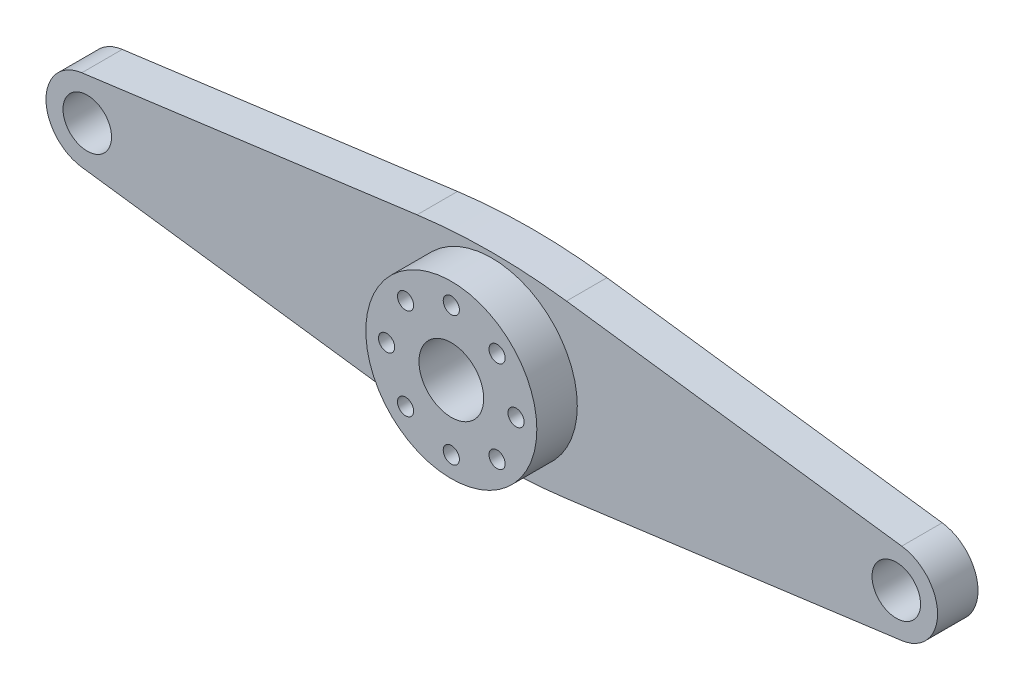
SolidWorks part; units mm, degrees
material "ABS"
ref_plane "Płaszczyzna przednia" through (0, 0, 0) normal (0, 0, 1) x (1, 0, 0)
ref_plane "Płaszczyzna górna" through (0, 0, 0) normal (0, 1, 0) x (1, 0, 0)
ref_plane "Płaszczyzna prawa" through (0, 0, 0) normal (1, 0, 0) x (0, 0, -1)
sketch "Szkic1" plane through (0, 0, 0) normal (0, 0, 1) x (1, 0, 0)
  line L0 (-44.521, 0) -> (57.4684, 0) construction
  line L1 (0, 0) -> (0, 26.3225) construction
  line L2 (-50.6729, 5.0557) -> (-9.2351, 10.5708)
  line L3 (-50.6729, -5.0557) -> (-9.2351, -10.5708)
  line L4 (50.6729, -5.0557) -> (9.2351, -10.5708)
  line L5 (50.6729, 5.0557) -> (9.2351, 10.5708)
  circle A0 centre (0, 0) radius 4
  circle A1 centre (-5.6569, 5.6569) radius 1
  circle A2 centre (-8, 0) radius 1
  circle A3 centre (0, 8) radius 1
  circle A4 centre (5.6569, 5.6569) radius 1
  circle A5 centre (-50, 0) radius 3
  circle A6 centre (50, 0) radius 3
  arc A7 (-50.6729, 5.0557) -> (-50.6729, -5.0557) centre (-50, 0) ccw
  arc A8 (50.6729, 5.0557) -> (50.6729, -5.0557) centre (50, 0) cw
  arc A9 (-9.2351, 10.5708) -> (9.2351, 10.5708) centre (0, -58.8174) cw
  arc A10 (-9.2351, -10.5708) -> (9.2351, -10.5708) centre (0, 58.8174) ccw
  circle A11 centre (8, 0) radius 1
  circle A12 centre (5.6569, -5.6569) radius 1
  circle A13 centre (0, -8) radius 1
  circle A14 centre (-5.6569, -5.6569) radius 1
  circle A15 centre (0, 0) radius 10.5708
  point P16 (0, 0)
  point P28 (0, 11.7999)
  point P31 (0, -11.7999)
  point P41 (0, 0)
  dimension "D1" = 8
  dimension "D2" = 50
  dimension "D3" = 8
  dimension "D4" = 6
  dimension "D5" = 2
  dimension "D6" = 21.1415
  dimension "D7" = 70
  dimension "D8" = 5.1002
  dimension "D9" = 5.6569
  dimension "D10" = 9.2351
extrude "Dodanie-wyciągnięcie1" add sketch "Szkic1" along normal blind 5 contours L3 A10 L4 A8 L5 A9 L2 A7 A15 A6 A5 | A15 A0 A1 A2 A3 A4 A11 A12 A13 A14 region at (-29.8056, 6.6986, 0) region at (-10.2718, 0, 0)
extrude "Dodanie-wyciągnięcie2" add sketch "Szkic1<3>" along normal blind 10 contours A15 A0 A1 A2 A3 A4 A11 A12 A13 A14 region at (-10.2718, 0, 0)
sketch "Szkic1<3>" plane through (0, 0, 0) normal (0, 0, 1) x (1, 0, 0) same geometry as "Szkic1"
